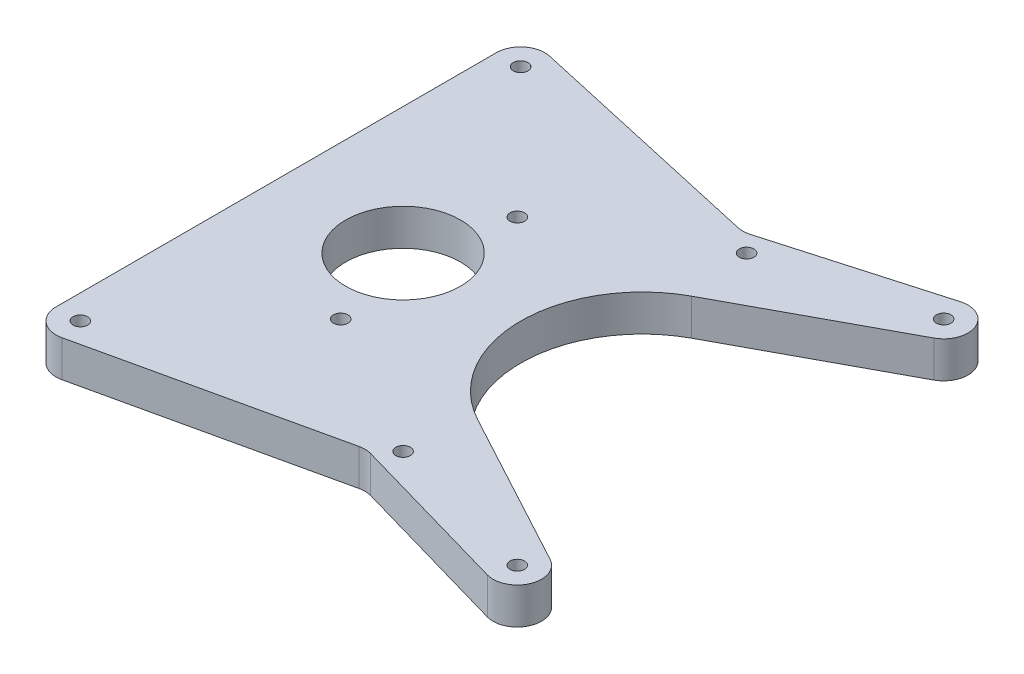
SolidWorks part; units mm, degrees
material "Alloy Steel"
ref_plane "Front Plane" through (0, 0, 0) normal (0, 0, 1) x (1, 0, 0)
ref_plane "Top Plane" through (0, 0, 0) normal (0, 1, 0) x (1, 0, 0)
ref_plane "Right Plane" through (0, 0, 0) normal (1, 0, 0) x (0, 0, -1)
sketch "Sketch2" plane through (0, 0, 0) normal (0, 1, 0) x (1, 0, 0)
  line L2 (62.5, 0) -> (25, 0) construction
  line L3 (25, 0) -> (0, 0) construction
  line L4 (62.5, 0) -> (179.6744, 0) construction
  line L5 (0, 0) -> (44.9013, 44.9013) construction
  line L6 (39.4146, 55.733) -> (62.5, 0) construction
  line L9 (62.5, 0) -> (85.5854, 55.733) construction
  line L10 (62.5, 0) -> (6.767, 23.0854) construction
  line L11 (0, 0) -> (-19.393, 0) construction
  line L12 (83.8387, 61.8381) -> (41.1613, 49.628)
  line L13 (38.0274, 49.5364) -> (-25.449, 63.7472)
  line L14 (0, 0) -> (-26.8363, 57.5505) construction
  line L15 (-25.449, -63.7472) -> (38.0274, -49.5364)
  line L16 (41.1613, -49.628) -> (83.8387, -61.8381)
  line L17 (0, 0) -> (44.9013, -44.9013) construction
  line L18 (-33.1863, 57.5505) -> (-33.1863, -57.5505)
  line L19 (0, 0) -> (-26.8363, -57.5505) construction
  line L21 (47.4315, 27.9464) -> (88.5991, 50.1438)
  line L22 (47.4315, -27.9464) -> (88.5991, -50.1438)
  arc A0 (47.4315, 27.9464) -> (47.4315, -27.9464) centre (62.5, 0) ccw
  circle A8 centre (6.767, 23.0854) radius 1.905
  circle A9 centre (85.5854, 55.733) radius 1.905
  circle A12 centre (85.5854, -55.733) radius 1.905
  circle A13 centre (6.767, -23.0854) radius 1.905
  circle A16 centre (0, 0) radius 25 construction
  circle A21 centre (85.5854, 55.733) radius 6.35
  circle A22 centre (85.5854, -55.733) radius 6.35
  circle A28 centre (0, 0) radius 15.0125
  circle A29 centre (-26.8363, 57.5505) radius 1.905
  circle A30 centre (44.9013, 44.9013) radius 1.905
  circle A33 centre (-26.8363, -57.5505) radius 1.905
  circle A34 centre (-26.8363, 57.5505) radius 6.35
  circle A35 centre (-26.8363, -57.5505) radius 6.35
  circle A37 centre (44.9013, -44.9013) radius 1.905
  circle A38 centre (39.4146, 55.733) radius 6.35
  circle A39 centre (39.4146, -55.733) radius 6.35
  dimension "D2" = 31.75
  dimension "D11" = 63.5
  dimension "D17" = 50
  dimension "D4" = 45
  dimension "D3" = 30.025
  dimension "D10" = 12.7
  dimension "D9" = 3.81
  dimension "D5" = 37.5
  dimension "D6" = 25
  dimension "D7" = 67.5
  dimension "D8" = 22.5
  dimension "D12" = 60.325
  dimension "D14" = 65
extrude "Boss-Extrude1" add sketch "Sketch2" along normal mid plane 9.525 contours A22 L22 A0 L21 A21 A16 | A13 | A22 A12 | A21 A9 | A8 | A34 A29 | A35 A33 region at (78.071, 0, -52.6742) region at (89.3003, 0, -60.6598) region at (-22.0201, 0, -61.4077) region at (90.8837, 0, 52.5704) region at (-26.8363, 0, 51.3801) region at (8.7329, 0, -23.2814)
ref_axis "Turbine Axis" through (0, 5.2388, 0) along (0, -1, 0)
ref_axis "Pump Axis" through (62.5, 4.7625, 0) along (0, -1, 0)
sketch "Sketch3" plane through (0, 0, 0) normal (0, 1, 0) x (1, 0, 0)
  line L0 (0, 0) -> (-63.5, 0) construction
  line L1 (-63.5, -88.9) -> (114.3, -88.9)
  line L2 (-63.5, -88.9) -> (-63.5, 88.9)
  line L3 (-63.5, 88.9) -> (114.3, 88.9)
  line L4 (114.3, -88.9) -> (114.3, 88.9)
  point P5 (-63.5, 0)
  dimension "D1" = 177.8
  dimension "D2" = 63.5
